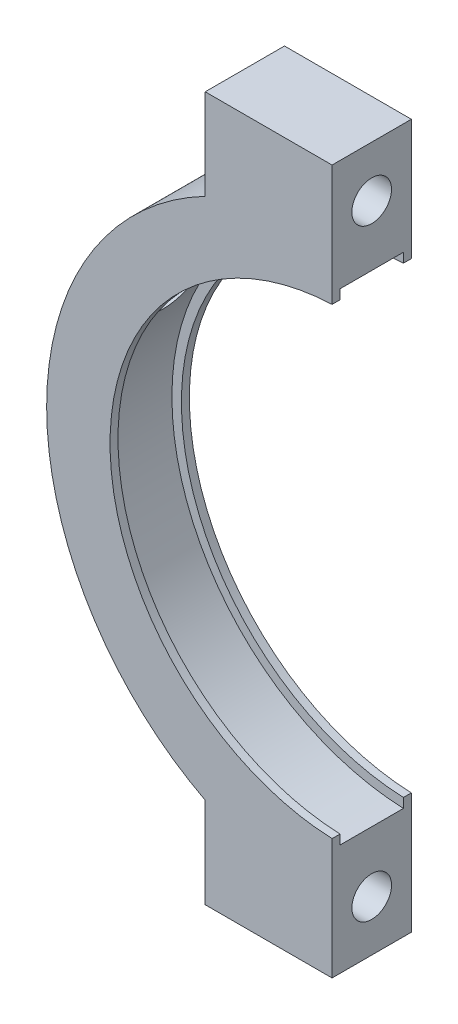
SolidWorks part; units mm, degrees
ref_plane "Front Plane" through (0, 0, 0) normal (0, 0, 1) x (1, 0, 0)
ref_plane "Top Plane" through (0, 0, 0) normal (0, 1, 0) x (1, 0, 0)
ref_plane "Right Plane" through (0, 0, 0) normal (1, 0, 0) x (0, 0, -1)
sketch "Sketch1" plane through (0, 0, 0) normal (0, 0, 1) x (1, 0, 0)
  line L6 (0, 0) -> (50000, 0) construction
  line L7 (0, 0) -> (0, 50000) construction
  line L8 (-3, 111) -> (-43, 111)
  line L9 (-3, -111) -> (-43, -111)
  line L10 (-43, 111) -> (-43, 82.4621)
  line L11 (-43, -111) -> (-43, -82.4621)
  line L12 (-3, 111) -> (-3, 72.9383)
  line L13 (-3, -111) -> (-3, -72.9383)
  arc A2 (-3, 72.9383) -> (-3, -72.9383) centre (0, 0) ccw
  arc A3 (-3, 75.9408) -> (-3, -75.9408) centre (0, 0) ccw
  arc A4 (-3, 92.9516) -> (-3, -92.9516) centre (0, 0) ccw
  dimension "D1" = 73
  dimension "D2" = 76
  dimension "D3" = 93
  dimension "D4" = 40
  dimension "D5" = 3
  dimension "D6" = 222
extrude "Boss-Extrude1" add sketch "Sketch1" along normal mid plane 25 contours L12 A4 L13 A3 | A4 L12 L8 L10 | A4 L11 L9 L13 region at (-24.5949, 99.9389, 0) region at (-5.0654, 84.4462, 0) region at (-24.5949, -99.9389, 0)
extrude "Boss-Extrude2" add sketch "Sketch1<3>" along normal blind 2.5 from offset 10 contours L12 A3 L13 A2 region at (-4.6851, 74.4395, 0)
sketch "Sketch1<3>" plane through (0, 0, 0) normal (0, 0, 1) x (1, 0, 0) same geometry as "Sketch1"
hole_wizard "Ø12.0mm Dowel Hole1" positions "Sketch3" profile "Sketch4" hole size "Ø12.0" standard "ISO" end condition through all
sketch "Sketch3" plane through (-3, 0, 0) normal (1, 0, 0) x (0, 0, -1)
  line L0 (0, 0) -> (54.4803, 0) construction
  line L1 (0, 0) -> (0, 95) construction
  point P0 (0, 95)
  point P2 (0, -95)
  point P14 (0, 0)
  point P15 (0, 93.9136)
  point P16 (0, 0)
  dimension "D1" = 190
sketch "Sketch4" plane through (-3, 95, 0) normal (0, 1, 0) x (0, 0, -1)
  line L0 (0, 0) -> (0, 90)
  line L1 (0, 90) -> (6.25, 90)
  line L2 (6.25, 90) -> (6.25, 0)
  line L5 (6.25, 0) -> (0, 0)
  line L11 (0, -6.35) -> (0, 107.95) construction
  dimension "Thru Hole Dia." = 12.5
  dimension "Thru Hole Depth" = 90
mirror "Mirror2" about plane through (0, 0, 0) normal (0, 0, 1) of "Boss-Extrude2"
sketch "Sketch5" plane through (0, 0, 0) normal (0, 0, 1) x (1, 0, 0)
  line L0 (0, 0) -> (-93, 0) construction
  line L1 (0, 0) -> (-80.5404, 46.5) construction
  arc A0 (-43, 82.4621) -> (-43, -82.4621) centre (0, 0) ccw construction
  point P3 (0, 0)
  point P8 (0, 0)
  point P9 (0, 0)
  dimension "D1" = 30
ref_plane "Plane1" through (-80.5404, 46.5, 0) normal (-0.866, 0.5, 0) x (0, 0, 1)
sketch "Sketch8" plane through (-80.5404, 46.5, 0) normal (-0.866, 0.5, 0) x (0, 0, 1)
  point P0 (0, 0)
  point P1 (0, 0)
hole_wizard "G1/4 Tapped Hole1" positions "Sketch8" profile "Sketch9" tap size "G1/4" standard "ISO" end condition through all
sketch "Sketch9" plane through (-80.5404, 46.5, 0) normal (0, 0, 1) x (-0.5, -0.866, 0)
  line L0 (0, 0) -> (0, 145.9019)
  line L1 (0, 145.9019) -> (5.9, 145.9019)
  line L2 (5.9, 145.9019) -> (5.9, 0)
  line L5 (5.9, 0) -> (0, 0)
  line L11 (0, -6.35) -> (0, 107.95) construction
  dimension "Thru Tap Drill Dia." = 11.8
  dimension "Thru Tap Drill Depth" = 145.9019
cosmetic thread "Hole Thread1" parameters "D2"=13.157
